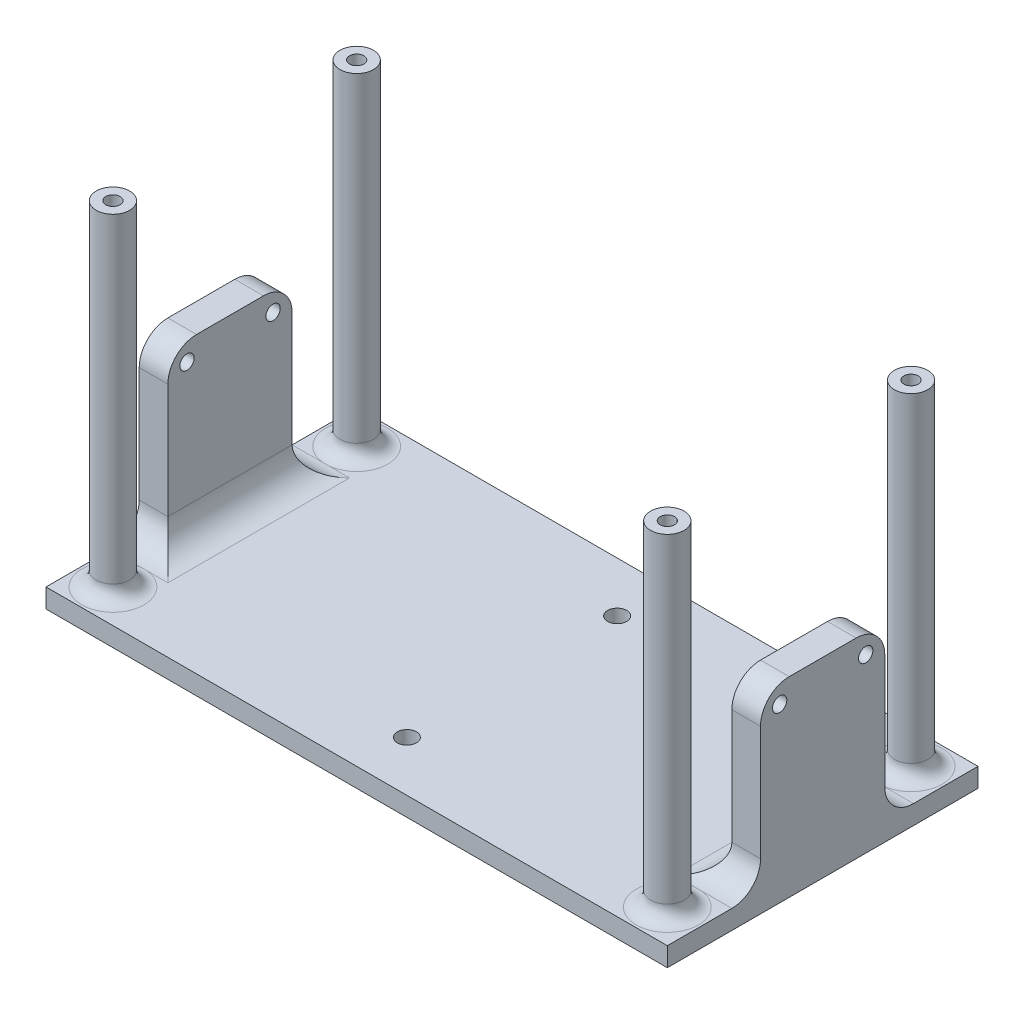
SolidWorks part; units mm, degrees
ref_plane "Front Plane" through (0, 0, 0) normal (0, 0, 1) x (1, 0, 0)
ref_plane "Top Plane" through (0, 0, 0) normal (0, 1, 0) x (1, 0, 0)
ref_plane "Right Plane" through (0, 0, 0) normal (1, 0, 0) x (0, 0, -1)
sketch "Sketch1" plane through (0, 0, 0) normal (0, 1, 0) x (1, 0, 0)
  line L1 (-65, 32.5) -> (65, 32.5)
  line L2 (-65, 32.5) -> (-65, -32.5)
  line L3 (-65, -32.5) -> (65, -32.5)
  line L4 (65, 32.5) -> (65, -32.5)
  line L5 (-65, 32.5) -> (65, -32.5) construction
  line L6 (-65, -32.5) -> (65, 32.5) construction
  point P0 (0, 0)
  dimension "D1" = 130
  dimension "D2" = 65
extrude "Boss-Extrude1" add sketch "Sketch1" against normal blind 4
sketch "Sketch4" plane through (0, 0, 0) normal (0, 1, 0) x (1, 0, 0)
  line L0 (65, 32.5) -> (-65, 32.5) construction
  line L1 (-65, 32.5) -> (-65, -32.5) construction
  line L2 (65, -32.5) -> (65, 32.5) construction
  line L3 (0, 32.5) -> (0, -32.5) construction
  line L4 (-65, -32.5) -> (65, -32.5) construction
  circle A0 centre (-58, 25.5) radius 3.5
  circle A1 centre (-58, 25.5) radius 1.5
  circle A2 centre (58, 25.5) radius 3.5
  circle A3 centre (58, 25.5) radius 1.5
  circle A4 centre (-58, -25.5) radius 3.5
  circle A5 centre (-58, -25.5) radius 1.5
  circle A6 centre (58, -25.5) radius 3.5
  circle A7 centre (58, -25.5) radius 1.5
  dimension "D1" = 7
  dimension "D2" = 7
  dimension "D3" = 7
  dimension "D4" = 7
  dimension "D5" = 7
  dimension "D6" = 7
  dimension "D7" = 7
  dimension "D8" = 7
  dimension "D9" = 7
  dimension "D10" = 3
  dimension "D11" = 7
  dimension "D12" = 3
  dimension "D13" = 7
  dimension "D14" = 3
  dimension "D15" = 7
  dimension "D16" = 3
extrude "Boss-Extrude3" add sketch "Sketch4" along normal blind 70
sketch "Sketch5" plane through (0, 0, 0) normal (0, 1, 0) x (1, 0, 0)
  line L0 (65, -32.5) -> (65, 32.5) construction
  line L1 (59, 13) -> (65, 13)
  line L2 (59, 13) -> (59, -13)
  line L3 (59, -13) -> (65, -13)
  line L4 (65, 13) -> (65, -13)
  line L5 (59, 13) -> (65, -13) construction
  line L6 (59, -13) -> (65, 13) construction
  point P0 (62, 0)
  dimension "D1" = 6
  dimension "D2" = 26
extrude "Boss-Extrude5" add sketch "Sketch5<2>" along normal blind 36
sketch "Sketch5<2>" plane through (0, 0, 0) normal (0, 1, 0) x (1, 0, 0) same geometry as "Sketch5"
extrude "Boss-Extrude4" add sketch "Sketch5" along normal blind 36
sketch "Sketch6" plane through (65, 0, 0) normal (1, 0, 0) x (0, 0, -1)
sketch "Sketch7" plane through (65, 0, 0) normal (1, 0, 0) x (0, 0, -1)
  line L1 (-13, 36) -> (-13, 0) construction
  line L2 (-13, 36) -> (13, 36) construction
  line L3 (13, 36) -> (13, 0) construction
  circle A0 centre (-9, 32) radius 1.5
  circle A1 centre (9, 32) radius 1.5
  dimension "D1" = 3
  dimension "D2" = 3
  dimension "D3" = 4
  dimension "D4" = 4
  dimension "D5" = 4
  dimension "D6" = 4
extrude "Cut-Extrude2" cut sketch "Sketch7" against normal blind 10
fillet "Fillet1" radius 6 5 edges at (59, 0, 0) (62, 0, -13) (62, 0, 13) (62, 36, 13) (62, 36, -13)
mirror "Mirror1" about plane through (0, 0, 0) normal (1, 0, 0) of "Cut-Extrude2", "Boss-Extrude5", "Fillet1"
sketch "Sketch10" plane through (0, 0, 0) normal (0, 1, 0) x (1, 0, 0)
  line L0 (0, 0) -> (0, 22) construction
  line L1 (-25, 0) -> (25, 0) construction
  line L2 (-40.7, 0) -> (40.7, 0) construction
  circle A0 centre (0, 22) radius 2
  circle A1 centre (0, -22) radius 2
  point P6 (0, 0)
  dimension "D1" = 4
  dimension "D2" = 22
  dimension "D3" = 50
extrude "Cut-Extrude3" cut sketch "Sketch10" against normal blind 10
fillet "Fillet2" radius 3 4 edges at (58, 0, 29) (58, 0, -22) (-58, 0, -22) (-58, 0, 29)
